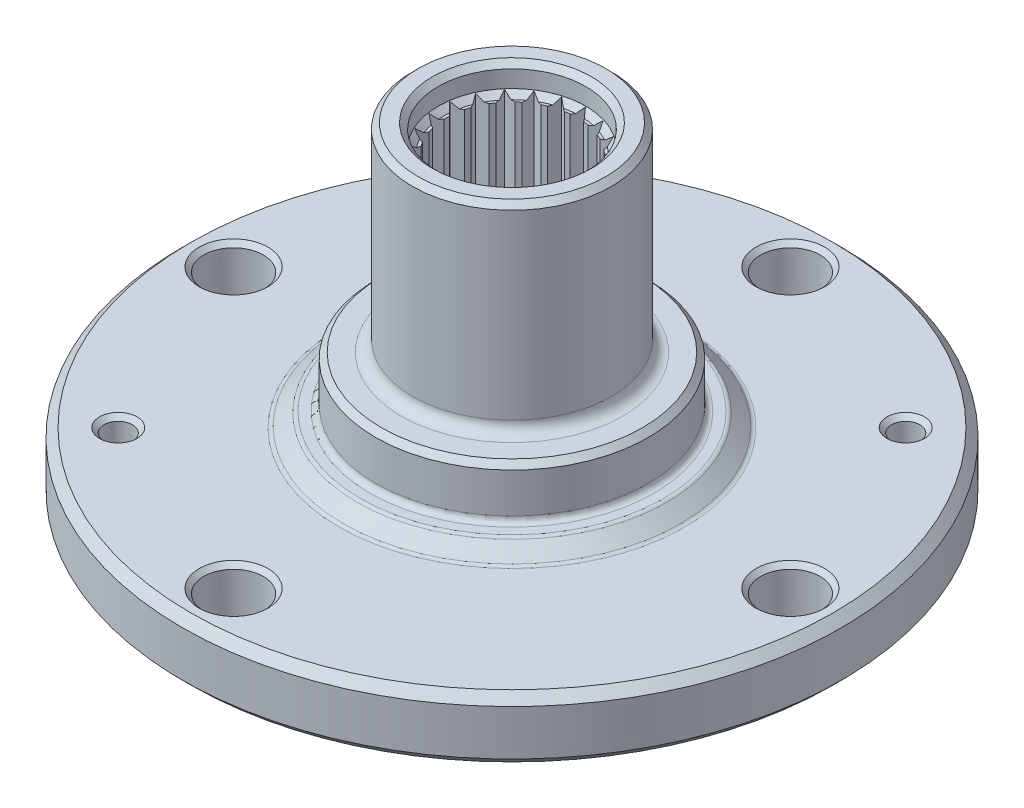
SolidWorks part; units mm, degrees
ref_plane "Plano frontal" through (0, 0, 0) normal (0, 0, 1) x (1, 0, 0)
ref_plane "Plano superior" through (0, 0, 0) normal (0, 1, 0) x (1, 0, 0)
ref_plane "Plano direito" through (0, 0, 0) normal (1, 0, 0) x (0, 0, -1)
sketch "Esboço1" plane through (0, 0, 0) normal (0, 0, 1) x (1, 0, 0)
  line L0 (9.29, -31.5682) -> (9.29, 39.7362) construction
  line L1 (22.29, 46.5) -> (22.29, 41.5)
  line L2 (22.29, 41.5) -> (20.79, 41.5)
  line L3 (20.79, 41.5) -> (20.79, -12)
  line L4 (20.79, -12) -> (32.29, -12)
  line L5 (32.29, -12) -> (32.29, -22)
  line L6 (32.29, -22) -> (34.79, -31)
  line L7 (34.79, -31) -> (38.29, -31)
  line L8 (38.29, -17) -> (38.29, -31)
  line L9 (38.29, -17) -> (38.79, -17)
  line L10 (38.79, -17) -> (38.79, -11)
  line L11 (38.79, -11) -> (67.29, -11)
  line L12 (67.29, -11) -> (67.29, 0)
  line L13 (67.29, 0) -> (39.29, 0)
  line L14 (39.29, 0) -> (36.29, 2.5)
  line L15 (36.29, 2.5) -> (33.29, 2.5)
  line L16 (33.29, 2.5) -> (33.29, 11.5)
  line L17 (33.29, 11.5) -> (26.79, 11.5)
  line L18 (26.79, 11.5) -> (26.79, 46.5)
  line L19 (26.79, 46.5) -> (22.29, 46.5)
  point P24 (32.0817, -27.5858)
  point P25 (37.8966, -32.1635)
  dimension "D1" = 35
  dimension "D2" = 44
  dimension "D3" = 20
  dimension "D4" = 11
  dimension "D5" = 77.5
  dimension "D6" = 10
  dimension "D7" = 19
  dimension "D8" = 5
  dimension "D9" = 11.5
  dimension "D10" = 13
  dimension "D11" = 17.5
  dimension "D12" = 24
  dimension "D13" = 27
  dimension "D14" = 30
  dimension "D15" = 23
  dimension "D16" = 25.5
  dimension "D17" = 29
  dimension "D18" = 29.5
  dimension "D19" = 6
  dimension "D20" = 58
revolve "Revolução1" add sketch "Esboço1" angle 360 about L0
sketch "Esboço2" plane through (0, -12, 0) normal (0, -1, 0) x (1, 0, 0)
  line L0 (9.29, 12.9208) -> (7.89, 11.1708)
  line L1 (9.29, 12.9208) -> (10.69, 11.1708)
  line L2 (12.9302, 12.3974) -> (11.0939, 11.1127)
  line L3 (20.79, 0) -> (9.29, 0) construction
  line L4 (9.29, 0) -> (9.29, 12.9208) construction
  line L5 (10.69, 11.1708) -> (7.89, 11.1708)
  line L6 (12.9302, 12.3974) -> (13.7805, 10.3239)
  line L7 (13.7805, 10.3239) -> (11.0939, 11.1127)
  line L8 (16.2755, 10.8697) -> (14.1516, 10.1544)
  line L9 (16.2755, 10.8697) -> (16.5072, 8.6406)
  line L10 (16.5072, 8.6406) -> (14.1516, 10.1544)
  line L11 (19.0549, 8.4613) -> (16.8155, 8.3734)
  line L12 (19.0549, 8.4613) -> (18.6491, 6.2573)
  line L13 (18.6491, 6.2573) -> (16.8155, 8.3734)
  line L14 (21.0432, 5.3675) -> (18.8697, 5.914)
  line L15 (21.0432, 5.3675) -> (20.0329, 3.367)
  line L16 (20.0329, 3.367) -> (18.8697, 5.914)
  line L17 (22.0793, 1.8388) -> (20.1479, 2.9755)
  line L18 (22.0793, 1.8388) -> (20.5463, 0.204)
  line L19 (20.5463, 0.204) -> (20.1479, 2.9755)
  line L20 (22.0793, -1.8388) -> (20.5463, -0.204)
  line L21 (22.0793, -1.8388) -> (20.1479, -2.9755)
  line L22 (20.1479, -2.9755) -> (20.5463, -0.204)
  line L23 (21.0432, -5.3675) -> (20.0329, -3.367)
  line L24 (21.0432, -5.3675) -> (18.8697, -5.914)
  line L25 (18.8697, -5.914) -> (20.0329, -3.367)
  line L26 (19.0549, -8.4613) -> (18.6491, -6.2573)
  line L27 (19.0549, -8.4613) -> (16.8155, -8.3734)
  line L28 (16.8155, -8.3734) -> (18.6491, -6.2573)
  line L29 (16.2755, -10.8697) -> (16.5072, -8.6406)
  line L30 (16.2755, -10.8697) -> (14.1516, -10.1544)
  line L31 (14.1516, -10.1544) -> (16.5072, -8.6406)
  line L32 (12.9302, -12.3974) -> (13.7805, -10.3239)
  line L33 (12.9302, -12.3974) -> (11.0939, -11.1127)
  line L34 (11.0939, -11.1127) -> (13.7805, -10.3239)
  line L35 (9.29, -12.9208) -> (10.69, -11.1708)
  line L36 (9.29, -12.9208) -> (7.89, -11.1708)
  line L37 (7.89, -11.1708) -> (10.69, -11.1708)
  line L38 (5.6498, -12.3974) -> (7.4861, -11.1127)
  line L39 (5.6498, -12.3974) -> (4.7996, -10.3239)
  line L40 (4.7996, -10.3239) -> (7.4861, -11.1127)
  line L41 (2.3045, -10.8697) -> (4.4284, -10.1544)
  line L42 (2.3045, -10.8697) -> (2.0729, -8.6406)
  line L43 (2.0729, -8.6406) -> (4.4284, -10.1544)
  line L44 (-0.4749, -8.4613) -> (1.7645, -8.3734)
  line L45 (-0.4749, -8.4613) -> (-0.0691, -6.2573)
  line L46 (-0.0691, -6.2573) -> (1.7645, -8.3734)
  line L47 (-2.4631, -5.3675) -> (-0.2897, -5.914)
  line L48 (-2.4631, -5.3675) -> (-1.4529, -3.367)
  line L49 (-1.4529, -3.367) -> (-0.2897, -5.914)
  line L50 (-3.4993, -1.8388) -> (-1.5678, -2.9755)
  line L51 (-3.4993, -1.8388) -> (-1.9663, -0.204)
  line L52 (-1.9663, -0.204) -> (-1.5678, -2.9755)
  line L53 (-3.4993, 1.8388) -> (-1.9663, 0.204)
  line L54 (-3.4993, 1.8388) -> (-1.5678, 2.9755)
  line L55 (-1.5678, 2.9755) -> (-1.9663, 0.204)
  line L56 (-2.4631, 5.3675) -> (-1.4529, 3.367)
  line L57 (-2.4631, 5.3675) -> (-0.2897, 5.914)
  line L58 (-0.2897, 5.914) -> (-1.4529, 3.367)
  line L59 (-0.4749, 8.4613) -> (-0.0691, 6.2573)
  line L60 (-0.4749, 8.4613) -> (1.7645, 8.3734)
  line L61 (1.7645, 8.3734) -> (-0.0691, 6.2573)
  line L62 (2.3045, 10.8697) -> (2.0729, 8.6406)
  line L63 (2.3045, 10.8697) -> (4.4284, 10.1544)
  line L64 (4.4284, 10.1544) -> (2.0729, 8.6406)
  line L65 (5.6498, 12.3974) -> (4.7996, 10.3239)
  line L66 (5.6498, 12.3974) -> (7.4861, 11.1127)
  line L67 (7.4861, 11.1127) -> (4.7996, 10.3239)
  dimension "D1" = 1.4
  dimension "D2" = 1.75
  dimension "D3" = 22
extrude "Corte-extrusão3" cut sketch "Esboço2" against normal through all
chamfer "Chanfro1" distance 1 angle 45 1 edges at (9.29, 41.5, -13)
chamfer "Chanfro2" distance 1 angle 45 2 edges at (9.29, 46.5, -17.5) (9.29, 46.5, -13)
fillet "Filete1" radius 2 1 edges at (9.29, 11.5, -17.5)
chamfer "Chanfro3" distance 1 angle 45 1 edges at (9.29, 11.5, -24)
fillet "Filete2" radius 1 3 edges at (9.29, 0, -30) (9.29, 2.5, -27) (9.29, 2.5, -24)
chamfer "Chanfro4" distance 1.5 angle 45 2 edges at (9.29, -11, -58) (9.29, 0, -58)
fillet "Filete3" radius 1 2 edges at (9.29, -12, -23) (9.29, -11, -29.5)
fillet "Filete4" radius 0.5 1 edges at (9.29, -17, -29)
chamfer "Chanfro5" distance 1 angle 45 2 edges at (9.29, -31, -25.5) (9.29, -31, -29) first distance on face at (9.29, -31, -29) first distance on face at (9.29, -17.5, -29)
fillet "Filete5" radius 0.5 1 edges at (9.29, -30, -29)
chamfer "Chanfro6" distance 1 angle 20 22 edges at (4.5127, -12, -10.4608) (1.7591, -12, -8.6911) (-0.3844, -12, -6.2174) (-1.7442, -12, -3.2399) (-2.21, -12, 0) (-1.7442, -12, 3.2399) (-0.3844, -12, 6.2174) (1.7591, -12, 8.6911) (4.5127, -12, 10.4608) (7.6534, -12, 11.3829) (10.9266, -12, 11.3829) (14.0673, -12, 10.4608) (16.8209, -12, 8.6911) (18.9644, -12, 6.2174) (20.3242, -12, 3.2399) (20.79, -12, 0) (20.3242, -12, -3.2399) (18.9644, -12, -6.2174) (16.8209, -12, -8.6911) (14.0673, -12, -10.4608) (10.9266, -12, -11.3829) (7.6534, -12, -11.3829) first distance on face at (9.29, -12, -22)
sketch "Esboço3" plane through (0, -11, 0) normal (0, -1, 0) x (1, 0, 0)
  circle A0 centre (9.29, 0) radius 49 construction
  circle A1 centre (-39.71, 0) radius 5.25
  circle A3 centre (9.29, 49) radius 5.25
  circle A4 centre (43.9382, -34.6482) radius 2.5
  circle A5 centre (58.29, 0) radius 5.25
  circle A7 centre (9.29, -49) radius 5.25
  circle A8 centre (-25.3582, 34.6482) radius 2.5
  circle A9 centre (43.9382, 34.6482) radius 5.25 [skipped]
  circle A10 centre (-25.3582, -34.6482) radius 5.25 [skipped]
  circle A12 centre (43.9382, -34.6482) radius 5.25 [skipped]
  circle A13 centre (-25.3582, 34.6482) radius 5.25 [skipped]
  dimension "D1" = 98
  dimension "D2" = 10.5
  dimension "D4" = 5
  dimension "D5" = 5
  dimension "D3" = 8
extrude "Corte-extrusão4" cut sketch "Esboço3" against normal through all
chamfer "Chanfro7" distance 0.8 angle 45 12 edges at (-25.3582, 0, 37.1482) (-25.3582, -11, 32.1482) (9.29, 0, 54.25) (9.29, -11, 43.75) (58.29, 0, 5.25) (58.29, -11, -5.25) (43.9382, 0, -32.1482) (43.9382, -11, -37.1482) (9.29, 0, -43.75) (9.29, -11, -54.25) (-39.71, 0, 5.25) (-39.71, -11, -5.25)
